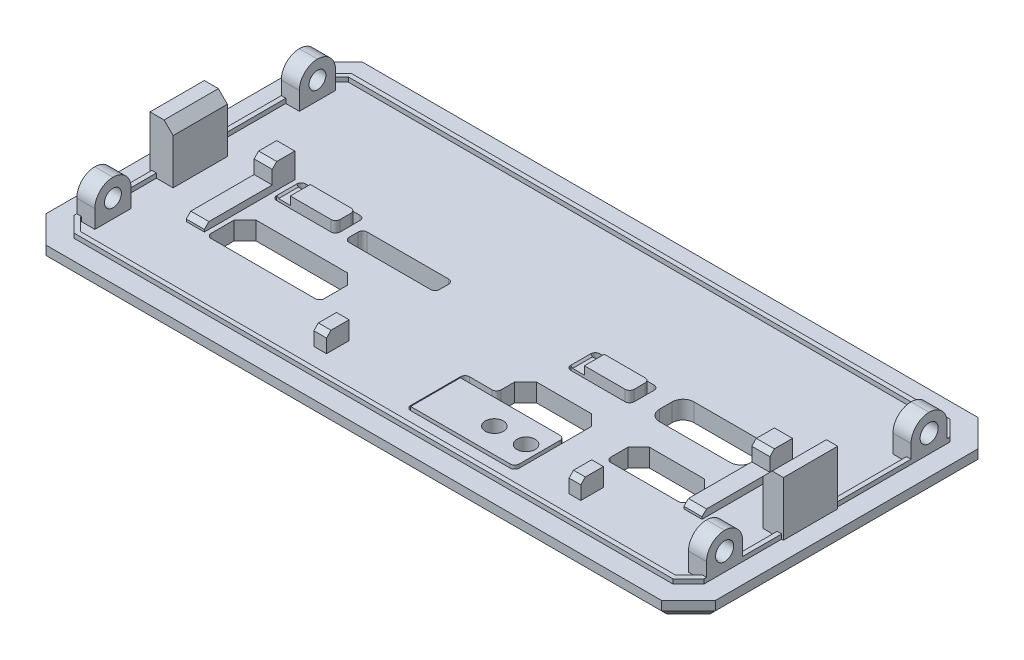
SolidWorks part; units mm, degrees
ref_plane "前视基准面" through (0, 0, 0) normal (0, 0, 1) x (1, 0, 0)
ref_plane "上视基准面" through (0, 0, 0) normal (0, 1, 0) x (1, 0, 0)
ref_plane "右视基准面" through (0, 0, 0) normal (1, 0, 0) x (0, 0, -1)
other "Configuration Table"
sketch "草图2" plane through (0, 0, 0) normal (0, 1, 0) x (1, 0, 0)
  line L0 (-36.7624, 30.764) -> (-33.7624, 33.764)
  line L1 (-36.7624, 1.764) -> (-33.7624, -1.236)
  line L2 (-33.7624, 33.764) -> (34.2376, 33.764)
  line L3 (-36.7624, 30.764) -> (-36.7624, 1.764)
  line L4 (-33.7624, -1.236) -> (34.2376, -1.236)
  line L5 (37.2376, 30.764) -> (37.2376, 1.764)
  line L6 (34.2376, -1.236) -> (37.2376, 1.764)
  line L7 (34.2376, 33.764) -> (37.2376, 30.764)
  point P5 (-36.7624, -1.236)
  point P7 (-36.7624, -1.236)
  point P8 (37.2376, 33.764)
  point P10 (37.2376, 33.764)
  point P11 (37.2376, -1.236)
  point P13 (-36.7624, 33.764)
  point P15 (-36.7624, 33.764)
  dimension "D1" = 74
  dimension "D2" = 35
extrude "凸台-拉伸1" add sketch "草图2" along normal blind 2
chamfer "倒角1" distance 1 angle 45 8 edges at (-36.7624, 0, -16.264) (0.2376, 0, -33.764) (0.2376, 0, 1.236) (37.2376, 0, -16.264) (-35.2624, 0, -32.264) (-35.2624, 0, -0.264) (35.7376, 0, -0.264) (35.7376, 0, -32.264)
sketch "草图3" plane through (0, 0, 0) normal (0, -1, 0) x (1, 0, 0)
  line L1 (-25.7624, -8.514) -> (-13.2624, -8.514)
  line L2 (-25.7624, -8.514) -> (-25.7624, -12.764)
  line L3 (-25.7624, -12.764) -> (-13.2624, -12.764)
  line L4 (-13.2624, -8.514) -> (-13.2624, -12.764)
  line L5 (1.7376, -3.064) -> (13.7376, -3.064)
  line L7 (5.2376, -12.764) -> (13.7376, -12.764)
  line L8 (13.7376, -3.064) -> (13.7376, -12.764)
  line L9 (17.7376, -9.164) -> (26.2376, -9.164)
  line L10 (17.7376, -9.164) -> (17.7376, -12.764)
  line L11 (17.7376, -12.764) -> (26.2376, -12.764)
  line L12 (26.2376, -9.164) -> (26.2376, -12.764)
  line L13 (15.8376, -15.764) -> (26.0376, -15.764)
  line L14 (15.8376, -15.764) -> (15.8376, -19.564)
  line L15 (15.8376, -19.564) -> (26.0376, -19.564)
  line L16 (26.0376, -15.764) -> (26.0376, -19.564)
  line L17 (6.7376, -15.764) -> (13.7376, -15.764)
  line L18 (6.7376, -15.764) -> (6.7376, -18.964)
  line L19 (6.7376, -18.964) -> (13.7376, -18.964)
  line L20 (13.7376, -15.764) -> (13.7376, -18.964)
  line L21 (-25.7624, -15.764) -> (-18.7624, -15.764)
  line L22 (-25.7624, -15.764) -> (-25.7624, -18.964)
  line L23 (-25.7624, -18.964) -> (-18.7624, -18.964)
  line L24 (-18.7624, -15.764) -> (-18.7624, -18.964)
  line L25 (-17.7624, -15.764) -> (-7.7624, -15.764)
  line L26 (-17.7624, -15.764) -> (-17.7624, -17.764)
  line L27 (-17.7624, -17.764) -> (-7.7624, -17.764)
  line L28 (-7.7624, -15.764) -> (-7.7624, -17.764)
  line L29 (-36.7624, -30.764) -> (-36.7624, -1.764) construction
  line L30 (-34.7624, -15.764) -> (-43.2418, -15.764) construction
  line L31 (37.2376, -1.764) -> (37.2376, -30.764) construction
  line L32 (-35.2588, -12.764) -> (-41.1207, -12.764) construction
  line L33 (-33.7624, 1.236) -> (34.2376, 1.236) construction
  line L34 (34.2376, -33.764) -> (-33.7624, -33.764) construction
  line L35 (5.2376, -12.764) -> (5.2376, -9.564)
  line L36 (5.2376, -9.564) -> (1.7376, -9.564)
  line L37 (1.7376, -9.564) -> (1.7376, -3.064)
  point P28 (0, 0)
  point P34 (0, 0)
  dimension "D1" = 14
  dimension "D2" = 18
  dimension "D3" = 12.5
  dimension "D4" = 4.25
  dimension "D5" = 3.2
  dimension "D6" = 2
  dimension "D7" = 7
  dimension "D8" = 11
  dimension "D9" = 1
  dimension "D10" = 10
  dimension "D11" = 23.5
  dimension "D12" = 7
  dimension "D13" = 3.8
  dimension "D14" = 3.6
  dimension "D15" = 11
  dimension "D16" = 11.2
  dimension "D17" = 10.2
  dimension "D18" = 8.5
  dimension "D19" = 12
  dimension "D20" = 6.5
  dimension "D21" = 8.5
  dimension "D22" = 3.2
  dimension "D23" = 29
extrude "切除-拉伸1" cut sketch "草图3" against normal up to next
fillet "圆角1" radius 1.2 4 edges at (26.0376, 1, -15.764) (26.0376, 1, -19.564) (15.8376, 1, -19.564) (15.8376, 1, -15.764)
fillet "圆角2" radius 0.5 20 edges at (-7.7624, 1, -15.764) (-7.7624, 1, -17.764) (-17.7624, 1, -17.764) (-17.7624, 1, -15.764) (-18.7624, 1, -18.964) (-18.7624, 1, -15.764) (-25.7624, 1, -18.964) (-25.7624, 1, -15.764) (6.7376, 1, -18.964) (13.7376, 1, -18.964) (13.7376, 1, -15.764) (6.7376, 1, -15.764) (13.7376, 1, -3.064) (17.7376, 1, -9.164) (26.2376, 1, -9.164) (-13.2624, 1, -8.514) (-25.7624, 1, -8.514) (1.7376, 1, -3.064) (1.7376, 1, -9.564) (5.2376, 1, -9.564)
chamfer "倒角2" distance 1.2 angle 45 6 edges at (26.2376, 1, -12.764) (17.7376, 1, -12.764) (13.7376, 1, -12.764) (-13.2624, 1, -12.764) (-25.7624, 1, -12.764) (5.2376, 1, -12.764)
sketch "草图4" plane through (0, 0, 0) normal (0, -1, 0) x (1, 0, 0)
  line L0 (13.2376, -3.064) -> (2.2376, -3.064) construction
  line L1 (-22.7624, -16.264) -> (-19.2624, -16.264)
  line L2 (-22.7624, -16.264) -> (-22.7624, -18.464)
  line L3 (-22.7624, -18.464) -> (-19.2624, -18.464)
  line L4 (-19.2624, -16.264) -> (-19.2624, -18.464)
  line L5 (6.7376, -3.564) -> (13.2376, -3.564)
  line L6 (6.7376, -3.564) -> (6.7376, -9.064)
  line L7 (6.7376, -9.064) -> (13.2376, -9.064)
  line L8 (13.2376, -3.564) -> (13.2376, -9.064)
  line L9 (8.7376, -16.264) -> (13.2376, -16.264)
  line L10 (8.7376, -16.264) -> (8.7376, -18.464)
  line L11 (8.7376, -18.464) -> (13.2376, -18.464)
  line L12 (13.2376, -16.264) -> (13.2376, -18.464)
  line L13 (13.7376, -11.564) -> (13.7376, -3.564) construction
  line L15 (2.2376, -9.564) -> (4.7376, -9.564) construction
  line L16 (13.7376, -18.464) -> (13.7376, -16.264) construction
  line L17 (7.2376, -18.964) -> (13.2376, -18.964) construction
  line L18 (13.2376, -15.764) -> (7.2376, -15.764) construction
  line L19 (-19.2624, -15.764) -> (-25.2624, -15.764) construction
  line L20 (-25.2624, -18.964) -> (-19.2624, -18.964) construction
  line L21 (-18.7624, -18.464) -> (-18.7624, -16.264) construction
  dimension "D1" = 0.5
  dimension "D2" = 6.5
  dimension "0.5" = 0.5
  dimension "D3" = 0.5
  dimension "D4" = 0.5
  dimension "D5" = 0.5
  dimension "D6" = 0.5
  dimension "D7" = 4.5
  dimension "D8" = 0.5
  dimension "D9" = 0.5
  dimension "D10" = 0.5
  dimension "D11" = 3.5
extrude "凸台-拉伸2" add sketch "草图4" against normal blind 1 separate body
sketch "草图5" plane through (0, 1, 0) normal (0, 1, 0) x (1, 0, 0)
  line L0 (-25.7624, 18.464) -> (-25.7624, 16.264) construction
  line L1 (-19.2624, 16.264) -> (-25.7624, 16.264)
  line L2 (-19.2624, 16.264) -> (-19.2624, 18.464)
  line L3 (-19.2624, 18.464) -> (-25.7624, 18.464)
  line L4 (-25.7624, 16.264) -> (-25.7624, 18.464)
  line L5 (8.7376, 18.464) -> (13.2376, 18.464) construction
  line L6 (13.2376, 16.264) -> (6.7376, 16.264)
  line L7 (13.2376, 16.264) -> (13.2376, 18.464)
  line L8 (13.2376, 18.464) -> (6.7376, 18.464)
  line L9 (6.7376, 16.264) -> (6.7376, 18.464)
extrude "凸台-拉伸3" add sketch "草图5" along normal blind 0.8
sketch "草图16" plane through (0, 1.8, 0) normal (0, 1, 0) x (1, 0, 0)
  line L0 (13.2376, 18.464) -> (6.7376, 18.464) construction
  line L1 (13.2376, 16.264) -> (8.2376, 16.264)
  line L2 (13.2376, 16.264) -> (13.2376, 18.464)
  line L3 (13.2376, 18.464) -> (8.2376, 18.464)
  line L4 (8.2376, 16.264) -> (8.2376, 18.464)
  line L5 (-25.7624, 16.264) -> (-19.2624, 16.264) construction
  line L6 (-19.2624, 18.464) -> (-24.2624, 18.464)
  line L7 (-19.2624, 18.464) -> (-19.2624, 16.264)
  line L8 (-19.2624, 16.264) -> (-24.2624, 16.264)
  line L9 (-24.2624, 18.464) -> (-24.2624, 16.264)
  dimension "D1" = 5
extrude "凸台-拉伸10" add sketch "草图16" along normal blind 0.9
sketch "草图6" plane through (0, 1, 0) normal (0, 1, 0) x (1, 0, 0)
  line L2 (13.2376, 3.564) -> (1.7376, 3.564)
  line L3 (13.2376, 3.564) -> (13.2376, 9.064)
  line L4 (13.2376, 9.064) -> (1.7376, 9.064)
  line L5 (1.7376, 3.564) -> (1.7376, 9.064)
extrude "凸台-拉伸4" add sketch "草图6" along normal blind 0.9
fillet "圆角5" radius 1 3 edges at (6.7376, 1, -17.364) (-25.7624, 1, -17.364) (1.7376, 1, -6.314)
fillet "圆角3" radius 0.5 12 edges at (8.7376, 0.5, -16.264) (8.7376, 0.5, -18.464) (13.2376, 1.35, -18.464) (13.2376, 1.35, -16.264) (-19.2624, 1.35, -16.264) (-19.2624, 1.35, -18.464) (-22.7624, 0.5, -18.464) (-22.7624, 0.5, -16.264) (13.2376, 0.95, -3.564) (6.7376, 0.5, -3.564) (13.2376, 0.95, -9.064) (6.7376, 0.5, -9.064)
chamfer "倒角3" distance 0.2 angle 45 2 edges at (-25.7624, 1.8, -17.364) (6.7376, 1.8, -17.364)
sketch "草图7" plane through (0, 2, 0) normal (0, 1, 0) x (1, 0, 0)
  line L0 (34.2376, -1.236) -> (-33.7624, -1.236) construction
  line L1 (-7.8624, 6.364) -> (-9.2624, 6.364)
  line L2 (-7.8624, 6.364) -> (-7.8624, 3.864)
  line L3 (-7.8624, 3.864) -> (-9.2624, 3.864)
  line L4 (-9.2624, 6.364) -> (-9.2624, 3.864)
  line L5 (20.2376, 3.864) -> (18.9376, 3.864)
  line L6 (20.2376, 3.864) -> (20.2376, 6.364)
  line L7 (20.2376, 6.364) -> (18.9376, 6.364)
  line L8 (18.9376, 3.864) -> (18.9376, 6.364)
  line L9 (37.2376, 1.764) -> (37.2376, 30.764) construction
  line L10 (-36.7624, 1.764) -> (-36.7624, 30.764) construction
  dimension "D1" = 5.1
  dimension "D2" = 17
  dimension "D3" = 27.5
  dimension "D4" = 1.3
  dimension "D5" = 1.4
  dimension "D6" = 2.5
extrude "凸台-拉伸5" add sketch "草图7" along normal blind 2
sketch "草图11" plane through (0, 2, 0) normal (0, 1, 0) x (1, 0, 0)
  line L0 (-33.7624, -1.236) -> (34.2376, -1.236) construction
  line L1 (28.7376, 8.764) -> (26.7376, 8.764)
  line L2 (28.7376, 8.764) -> (28.7376, 18.764)
  line L3 (28.7376, 18.764) -> (26.7376, 18.764)
  line L4 (26.7376, 8.764) -> (26.7376, 18.764)
  line L5 (-26.2624, 8.764) -> (-28.2624, 8.764)
  line L6 (-26.2624, 8.764) -> (-26.2624, 18.764)
  line L7 (-26.2624, 18.764) -> (-28.2624, 18.764)
  line L8 (-28.2624, 8.764) -> (-28.2624, 18.764)
  line L9 (-36.7624, 30.764) -> (-36.7624, 1.764) construction
  line L10 (37.2376, 1.764) -> (37.2376, 30.764) construction
  dimension "D1" = 10
  dimension "D2" = 8.5
  dimension "D3" = 2
  dimension "D4" = 10
  dimension "D5" = 8.5
  dimension "D6" = 2
extrude "凸台-拉伸7" add sketch "草图11" along normal blind 0.75
sketch "草图12" plane through (0, 2.75, 0) normal (0, 1, 0) x (1, 0, 0)
  line L0 (26.7376, 18.764) -> (26.7376, 8.764) construction
  line L1 (28.7376, 18.764) -> (26.7376, 18.764)
  line L2 (28.7376, 18.764) -> (28.7376, 16.264)
  line L3 (28.7376, 16.264) -> (26.7376, 16.264)
  line L4 (26.7376, 18.764) -> (26.7376, 16.264)
  line L5 (-28.2624, 18.764) -> (-28.2624, 8.764) construction
  line L6 (-26.2624, 18.764) -> (-28.2624, 18.764)
  line L7 (-26.2624, 18.764) -> (-26.2624, 16.264)
  line L8 (-26.2624, 16.264) -> (-28.2624, 16.264)
  line L9 (-28.2624, 18.764) -> (-28.2624, 16.264)
  dimension "D1" = 2.5
extrude "凸台-拉伸8" add sketch "草图12" along normal blind 2
chamfer "倒角4" distance 0.5 angle 45 6 edges at (-8.5624, 4, -3.864) (19.5876, 4, -3.864) (-27.2624, 2.75, -8.764) (27.7376, 2.75, -8.764) (-27.2624, 4.75, -16.264) (27.7376, 4.75, -16.264)
sketch "草图8" plane through (0, 2, 0) normal (0, 1, 0) x (1, 0, 0)
  line L1 (35.0376, 2.964) -> (33.0376, 2.964)
  line L2 (35.0376, 2.964) -> (35.0376, 6.964)
  line L3 (35.0376, 6.964) -> (33.0376, 6.964)
  line L4 (33.0376, 2.964) -> (33.0376, 6.964)
  line L6 (35.0376, 25.564) -> (33.0376, 25.564)
  line L7 (35.0376, 25.564) -> (35.0376, 29.564)
  line L8 (35.0376, 29.564) -> (33.0376, 29.564)
  line L9 (33.0376, 25.564) -> (33.0376, 29.564)
  line L10 (-34.5624, 2.964) -> (-32.5624, 2.964)
  line L11 (-34.5624, 2.964) -> (-34.5624, 6.964)
  line L12 (-34.5624, 6.964) -> (-32.5624, 6.964)
  line L13 (-32.5624, 2.964) -> (-32.5624, 6.964)
  line L15 (-34.5624, 25.564) -> (-32.5624, 25.564)
  line L16 (-34.5624, 25.564) -> (-34.5624, 29.564)
  line L17 (-34.5624, 29.564) -> (-32.5624, 29.564)
  line L18 (-32.5624, 25.564) -> (-32.5624, 29.564)
  line L21 (-36.7624, 30.764) -> (-36.7624, 1.764) construction
  line L22 (34.2376, 33.764) -> (-33.7624, 33.764) construction
  line L23 (-33.7624, -1.236) -> (34.2376, -1.236) construction
  line L24 (37.2376, 1.764) -> (37.2376, 30.764) construction
  dimension "D1" = 4
  dimension "D2" = 2.2
  dimension "D3" = 4.2
  dimension "D4" = 4.2
  dimension "D5" = 2.2
  dimension "D6" = 2
extrude "凸台-拉伸6" add sketch "草图8" along normal blind 4
fillet "圆角4" radius 2 8 edges at (34.0376, 6, -6.964) (34.0376, 6, -2.964) (34.0376, 6, -29.564) (34.0376, 6, -25.564) (-33.5624, 6, -25.564) (-33.5624, 6, -29.564) (-33.5624, 6, -2.964) (-33.5624, 6, -6.964)
sketch "草图9" plane through (-34.5624, 0, 0) normal (-1, 0, 0) x (0, 0, 1)
  circle A0 centre (-4.964, 4) radius 1
  circle A1 centre (-27.564, 4) radius 1
  dimension "D1" = 2
extrude "切除-拉伸2" cut sketch "草图9" against normal up to next (2 mm away) draft 2
sketch "草图10" plane through (35.0376, 0, 0) normal (1, 0, 0) x (0, 0, -1)
  circle A0 centre (4.964, 4) radius 1
  circle A1 centre (27.564, 4) radius 1
  dimension "D1" = 2
extrude "切除-拉伸3" cut sketch "草图10" against normal up to next (2 mm away) draft 2
sketch "草图13" plane through (0, 2, 0) normal (0, 1, 0) x (1, 0, 0)
  line L0 (35.2376, 29.9355) -> (35.2376, 2.5924) construction
  line L1 (35.2376, 11.264) -> (32.9876, 11.264)
  line L2 (35.2376, 11.264) -> (35.2376, 17.264)
  line L3 (35.2376, 17.264) -> (32.9876, 17.264)
  line L4 (32.9876, 11.264) -> (32.9876, 17.264)
  line L5 (-34.7624, 2.5924) -> (-34.7624, 29.9355) construction
  line L6 (-34.7624, 11.264) -> (-32.2124, 11.264)
  line L7 (-34.7624, 11.264) -> (-34.7624, 17.264)
  line L8 (-34.7624, 17.264) -> (-32.2124, 17.264)
  line L9 (-32.2124, 11.264) -> (-32.2124, 17.264)
  line L10 (34.2376, -1.236) -> (-33.7624, -1.236) construction
  dimension "D1" = 12.5
  dimension "D2" = 6
  dimension "D3" = 2.25
  dimension "D4" = 2.55
extrude "凸台-拉伸9" add sketch "草图13" along normal blind 6
chamfer "倒角5" distance 1 angle 45 2 edges at (-32.2124, 8, -14.264) (32.9876, 8, -14.264)
sketch "草图14" plane through (0, 0, 0) normal (0, -1, 0) x (1, 0, 0)
  line L0 (7.0755, -6.314) -> (5.3752, -6.314) construction
  line L3 (13.2376, -8.564) -> (13.2376, -4.064) construction
  circle A0 centre (11.7376, -6.314) radius 1
  circle A1 centre (8.2376, -6.314) radius 1
  point P5 (13.2376, -6.314)
  dimension "D1" = 2
  dimension "D2" = 3.5
  dimension "D3" = 1.5
extrude "切除-拉伸4" cut sketch "草图14" against normal up to next
sketch "草图17" plane through (0, 2, 0) normal (0, 1, 0) x (1, 0, 0)
  line L8 (33.1192, 31.064) -> (-32.644, 31.064)
  line L9 (-32.644, 31.064) -> (-34.0624, 29.6456)
  line L10 (-34.0624, 29.6456) -> (-34.0624, 2.8823)
  line L11 (-34.0624, 2.8823) -> (-32.644, 1.464)
  line L12 (-32.644, 1.464) -> (33.1192, 1.464)
  line L13 (33.1192, 1.464) -> (34.5376, 2.8823)
  line L14 (34.5376, 2.8823) -> (34.5376, 29.6456)
  line L15 (34.5376, 29.6456) -> (33.1192, 31.064)
  line L16 (33.3264, 31.564) -> (-32.8511, 31.564)
  line L17 (-32.8511, 31.564) -> (-34.5624, 29.8527)
  line L18 (-34.5624, 29.8527) -> (-34.5624, 2.6752)
  line L19 (-34.5624, 2.6752) -> (-32.8511, 0.964)
  line L20 (-32.8511, 0.964) -> (33.3264, 0.964)
  line L21 (33.3264, 0.964) -> (35.0376, 2.6752)
  line L22 (35.0376, 2.6752) -> (35.0376, 29.8527)
  line L23 (35.0376, 29.8527) -> (33.3264, 31.564)
  line L24 (33.3264, 31.564) -> (-32.8511, 31.564)
  line L25 (-32.8511, 31.564) -> (-34.5624, 29.8527)
  line L26 (-34.5624, 29.8527) -> (-34.5624, 2.6752)
  line L27 (-34.5624, 2.6752) -> (-32.8511, 0.964)
  line L28 (-32.8511, 0.964) -> (33.3264, 0.964)
  line L29 (33.3264, 0.964) -> (35.0376, 2.6752)
  line L30 (35.0376, 2.6752) -> (35.0376, 29.8527)
  line L31 (35.0376, 29.8527) -> (33.3264, 31.564)
  dimension "D1" = 2.2
  dimension "D2" = 0.5
extrude "凸台-拉伸11" add sketch "草图17" along normal blind 0.5
